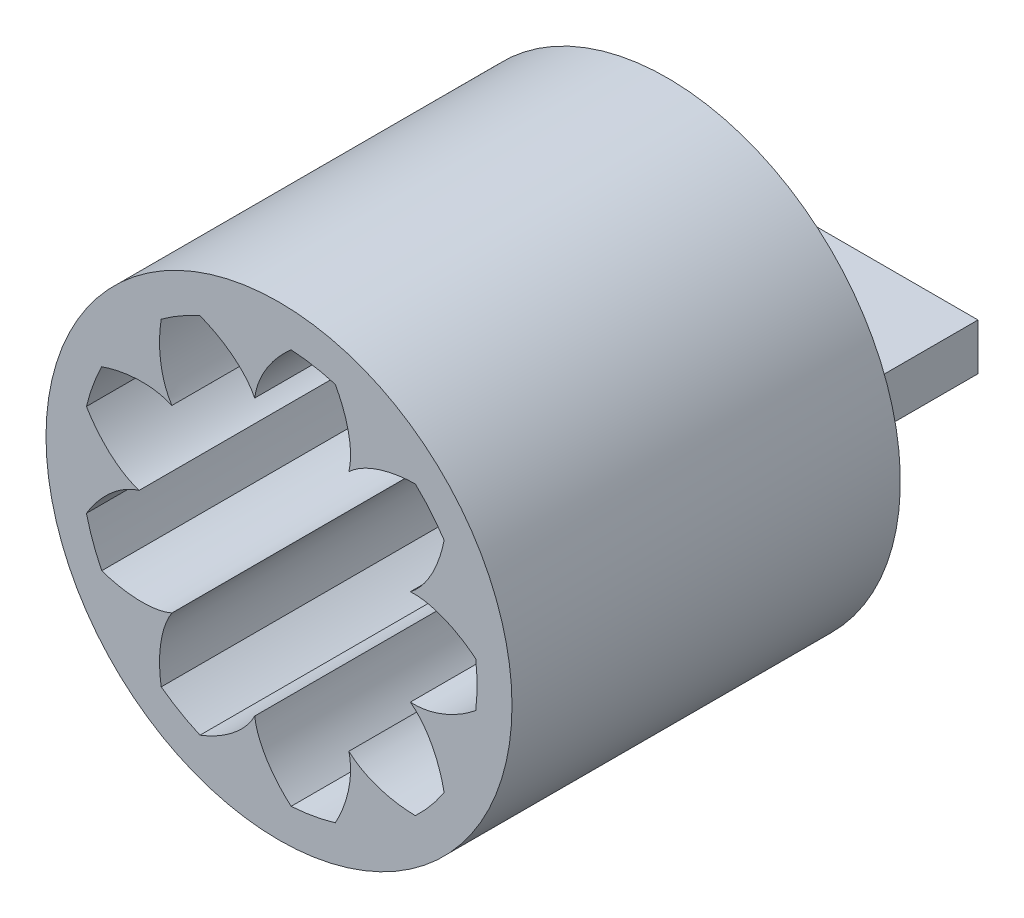
SolidWorks part; units mm, degrees
ref_plane "前视基准面" through (0, 0, 0) normal (0, 0, 1) x (1, 0, 0)
ref_plane "上视基准面" through (0, 0, 0) normal (0, 1, 0) x (1, 0, 0)
ref_plane "右视基准面" through (0, 0, 0) normal (1, 0, 0) x (0, 0, -1)
other "Configuration Table"
sketch "草图1" plane through (0, 0, 0) normal (0, 0, 1) x (1, 0, 0)
  line L0 (0, 0) -> (1.6914, 0.6156) construction
  line L1 (0, 0) -> (1.5832, 0.5954)
  line L2 (0, 0) -> (1.5832, -0.5954)
  line L3 (0, 0) -> (1.6914, -0.6156) construction
  line L4 (0, 0) -> (2.55, 0) construction
  line L5 (1.6914, 0.6156) -> (1.6914, -0.6156) construction
  circle A0 centre (0, 0) radius 1.65
  circle A1 centre (0, 0) radius 2.55
  circle A2 centre (0, 0) radius 1.6914 construction
  circle A3 centre (0, 0) radius 1.8 construction
  circle A4 centre (0, 0) radius 3
  spline S0 degree 4 poles (1.5832, 0.5954) (1.5953, 0.5999) (1.6299, 0.61) (1.6985, 0.6188) (1.8107, 0.6176) (1.9542, 0.5935) (2.1323, 0.5368) (2.3288, 0.4397) (2.527, 0.3033) (2.7182, 0.1281) (2.8863, -0.0692) (3.0309, -0.2841) (3.1583, -0.5243) (3.284, -0.8365) (3.3855, -1.2255) (3.4358, -1.6902) (3.4119, -2.2085) (3.3126, -2.7182) (3.1474, -3.2089) (2.918, -3.6756) (2.6387, -4.1089) (2.3029, -4.5102) (1.9385, -4.866) (1.5141, -5.1906) (1.1742, -5.4065) (0.7714, -5.6132) (0.5343, -5.7151) (0.2601, -5.8236) (0.1183, -5.8645) (-0.005, -5.9055) (-0.0434, -5.9147) (-0.0704, -5.9226) (-0.0848, -5.927) knots 0 0 0 0 0 0.005604 0.015718 0.02996 0.048734 0.068727 0.096889 0.125051 0.153212 0.181374 0.209535 0.237696 0.271429 0.327752 0.384075 0.440398 0.496721 0.553044 0.609367 0.66569 0.722013 0.778336 0.834659 0.890982 0.909091 0.954545 0.977273 0.988636 0.994318 1 1 1 1 1 construction
  spline S1 degree 4 poles (1.5832, 0.5954) (1.5953, 0.5999) (1.6299, 0.61) (1.6985, 0.6188) (1.8107, 0.6176) (1.9542, 0.5935) (2.1323, 0.5368) (2.3288, 0.4397) (2.527, 0.3033) (2.7182, 0.1281) (2.8863, -0.0692) (3.0309, -0.2841) (3.1583, -0.5243) (3.284, -0.8365) (3.3855, -1.2255) (3.4358, -1.6902) (3.4119, -2.2085) (3.3126, -2.7182) (3.1474, -3.2089) (2.918, -3.6756) (2.6387, -4.1089) (2.3029, -4.5102) (1.9385, -4.866) (1.5141, -5.1906) (1.1742, -5.4065) (0.8753, -5.5599) (0.734, -5.626) (0.6996, -5.6416) knots 0 0 0 0 0 0.005604 0.015718 0.02996 0.048734 0.068727 0.096889 0.125051 0.153212 0.181374 0.209535 0.237696 0.271429 0.327752 0.384075 0.440398 0.496721 0.553044 0.609367 0.66569 0.722013 0.778336 0.834659 0.890982 0.909091 0.909091 0.909091 0.909091 0.909091
  spline S2 degree 4 poles (1.5832, -0.5954) (1.5953, -0.5999) (1.6299, -0.61) (1.6985, -0.6188) (1.8107, -0.6176) (1.9542, -0.5935) (2.1323, -0.5368) (2.3288, -0.4397) (2.527, -0.3033) (2.7182, -0.1281) (2.8863, 0.0692) (3.0309, 0.2841) (3.1583, 0.5243) (3.284, 0.8365) (3.3855, 1.2255) (3.4358, 1.6902) (3.4119, 2.2085) (3.3126, 2.7182) (3.1474, 3.2089) (2.918, 3.6756) (2.6387, 4.1089) (2.3029, 4.5102) (1.9385, 4.866) (1.5141, 5.1906) (1.1742, 5.4065) (0.7714, 5.6132) (0.5343, 5.7151) (0.2601, 5.8236) (0.1183, 5.8645) (-0.005, 5.9055) (-0.0434, 5.9147) (-0.0704, 5.9226) (-0.0848, 5.927) knots 0 0 0 0 0 0.005604 0.015718 0.02996 0.048734 0.068727 0.096889 0.125051 0.153212 0.181374 0.209535 0.237696 0.271429 0.327752 0.384075 0.440398 0.496721 0.553044 0.609367 0.66569 0.722013 0.778336 0.834659 0.890982 0.909091 0.954545 0.977273 0.988636 0.994318 1 1 1 1 1 construction
  spline S3 degree 4 poles (1.5832, -0.5954) (1.5953, -0.5999) (1.6299, -0.61) (1.6985, -0.6188) (1.8107, -0.6176) (1.9542, -0.5935) (2.1323, -0.5368) (2.3288, -0.4397) (2.527, -0.3033) (2.7182, -0.1281) (2.8863, 0.0692) (3.0309, 0.2841) (3.1583, 0.5243) (3.284, 0.8365) (3.3855, 1.2255) (3.4358, 1.6902) (3.4119, 2.2085) (3.3126, 2.7182) (3.1474, 3.2089) (2.918, 3.6756) (2.6387, 4.1089) (2.3029, 4.5102) (1.9385, 4.866) (1.5141, 5.1906) (1.1742, 5.4065) (0.8753, 5.5599) (0.734, 5.626) (0.6996, 5.6416) knots 0 0 0 0 0 0.005604 0.015718 0.02996 0.048734 0.068727 0.096889 0.125051 0.153212 0.181374 0.209535 0.237696 0.271429 0.327752 0.384075 0.440398 0.496721 0.553044 0.609367 0.66569 0.722013 0.778336 0.834659 0.890982 0.909091 0.909091 0.909091 0.909091 0.909091
  point P16 (1.6914, 0)
  dimension "内啮合齿顶圆直径" = 3.3
  dimension "内啮合分度圆直径" = 3.6
  dimension "内啮合基圆直径" = 3.3829
  dimension "内啮合齿根圆直径" = 5.1
  dimension "外径" = 6
  dimension "渐开线镜像线夹角" = 20
extrude "凸台-拉伸1" add sketch "草图1" along normal blind 4 contours A4 | A0
extrude "切除-拉伸2" cut sketch "草图1<3>" along normal through all contours A0 S3 A1 S1 region at (2.0287, 0, 0)
sketch "草图1<3>" plane through (0, 0, 0) normal (0, 0, 1) x (1, 0, 0) same geometry as "草图1"
pattern_circular "阵列(圆周)1" count 9 over 360 about axis through (0, 0, 4) along (0, 0, 1) of "切除-拉伸2"
sketch "草图2" plane through (0, 0, 0) normal (0, 0, -1) x (-1, 0, 0)
  line L1 (-2, -0.3) -> (2, -0.3)
  line L2 (-2, -0.3) -> (-2, 0.3)
  line L3 (-2, 0.3) -> (2, 0.3)
  line L4 (2, -0.3) -> (2, 0.3)
  line L5 (-2, -0.3) -> (2, 0.3) construction
  line L6 (-2, 0.3) -> (2, -0.3) construction
  line L7 (0.3, -1.25) -> (-0.3, -1.25)
  line L8 (0.3, -1.25) -> (0.3, 1.25)
  line L9 (0.3, 1.25) -> (-0.3, 1.25)
  line L10 (-0.3, -1.25) -> (-0.3, 1.25)
  line L11 (0.3, -1.25) -> (-0.3, 1.25) construction
  line L12 (0.3, 1.25) -> (-0.3, -1.25) construction
  circle A0 centre (0, 0) radius 3
  circle A1 centre (0, 0) radius 3 construction
  dimension "D1" = 0.6
  dimension "D2" = 4
  dimension "D3" = 2.5
extrude "凸台-拉伸2" add sketch "草图2" along normal blind 1 contours A0
extrude "凸台-拉伸3" add sketch "草图2<3>" along normal blind 2 from surface contours L3 L4 L1 L2 starting at face at (-3, 0, -1)
sketch "草图2<3>" plane through (0, 0, 0) normal (0, 0, -1) x (-1, 0, 0) same geometry as "草图2"
extrude "凸台-拉伸4" add sketch "草图2<4>" along normal blind 1 from surface contours L10 L9 L8 L7 starting at face at (-3, 0, -1)
sketch "草图2<4>" plane through (0, 0, 0) normal (0, 0, -1) x (-1, 0, 0) same geometry as "草图2"
equation "\"m\"= 0.4'模数"
equation "\"z1\"= 9'外啮合齿轮数"
equation "\"a\"= 20度'压力角"
equation "\"z2\" = 9'内啮合齿轮数"
equation "\"hax\"= 1'齿顶高系数"
equation "\"cx\"= 0.25'顶隙系数"
equation "\"ha\"= \"hax\" * \"m\"'齿顶高"
equation "\"hf\"= ( \"hax\" + \"cx\" ) * \"m\"'齿根高"
equation "\"d1\"= \"m\" * \"z1\"'外啮合分度圆直径"
equation "\"da1\"= ( \"z1\" + 2 ) * \"m\"'外啮合齿顶圆直径"
equation "\"df1\"= \"d1\" - 2 * \"hf\"'外啮合齿根圆直径"
equation "\"db1\"= \"d1\" * cos ( \"a\" )'外啮合基圆直径"
equation "\"p\"= \"m\" * PI'齿距"
equation "\"d2\"= \"m\" * \"z2\"'内啮合分度圆直径"
equation "\"db2\"= \"d2\" * cos ( \"a\" )'内啮合基圆直径"
equation "\"da2\"= ( \"z2\" - 2 ) * \"m\"'内啮合齿顶圆直径"
equation "\"df2\"= \"d2\" + 2 * \"hf\"'内啮合齿根圆直径"
equation "\"内啮合齿顶圆直径@草图1\" = \"da2\" + 1 * \"hf\""
equation "\"内啮合齿根圆直径@草图1\" = \"df2\" + 1 * \"hf\""
equation "\"内啮合分度圆直径@草图1\"= \"d2\""
equation "\"内啮合基圆直径@草图1\"= \"db2\""
equation "\"渐开线镜像线夹角@草图1\"= 360度 / 4 / \"z2\" + 360度 / 4 / \"z2\""
equation "\"do\"= IIF ( \"edo\" >= ( \"df2\" + 1 ) , \"edo\" , ( \"df2\" + 1 ) )'外圈直径"
equation "\"h\"= 4'厚度"
equation "\"外径@草图1\"= \"do\""
equation "\"厚度@凸台-拉伸1\"= \"h\""
equation "\"内啮合齿轮数@阵列(圆周)1\"= \"z2\""
equation "\"edo\"= 6'期望的外圈直径"
